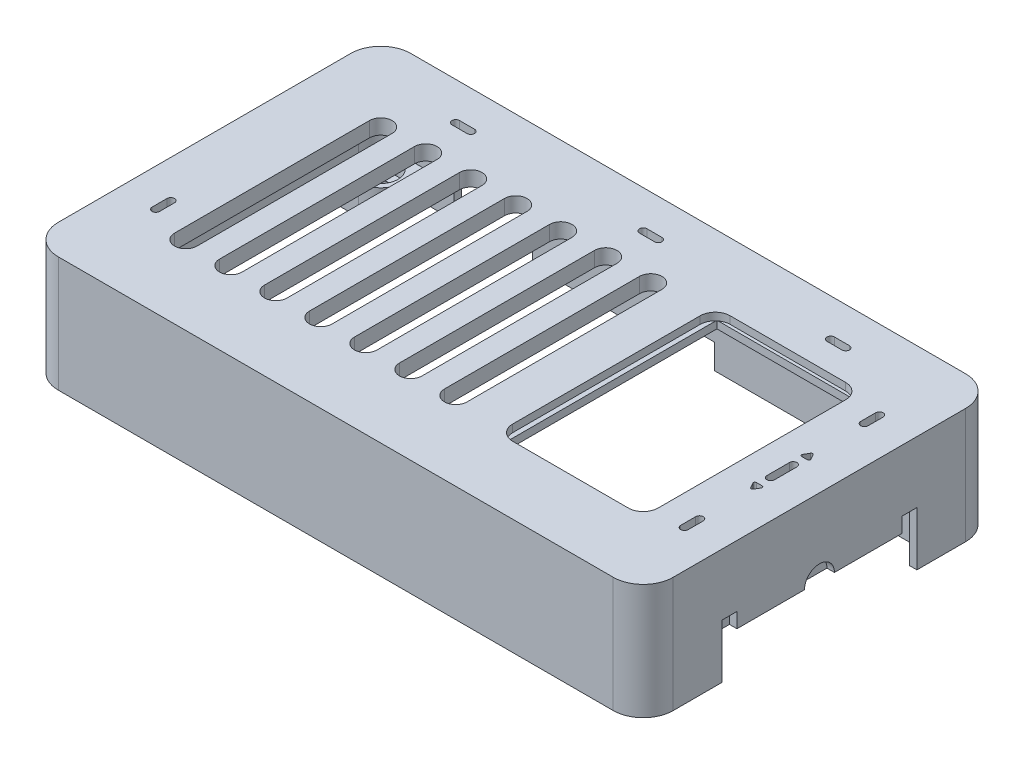
SolidWorks part; units mm, degrees
ref_plane "前视基准面" through (0, 0, 0) normal (0, 0, 1) x (1, 0, 0)
ref_plane "上视基准面" through (0, 0, 0) normal (0, 1, 0) x (1, 0, 0)
ref_plane "右视基准面" through (0, 0, 0) normal (1, 0, 0) x (0, 0, -1)
sketch "草图1" plane through (0, 0, 0) normal (0, 1, 0) x (1, 0, 0)
  line L0 (-1, -3) -> (-1, -42)
  line L1 (3, 0) -> (77, 0) construction
  line L2 (0, -3) -> (0, -42) construction
  line L3 (3, -45) -> (77, -45) construction
  line L4 (80, -3) -> (80, -42) construction
  line L5 (3, -46) -> (77, -46)
  line L6 (81, -3) -> (81, -42)
  line L7 (3, 1) -> (77, 1)
  arc A0 (3, -45) -> (0, -42) centre (3, -42) cw construction
  arc A1 (77, -45) -> (80, -42) centre (77, -42) ccw construction
  arc A2 (80, -3) -> (77, 0) centre (77, -3) ccw construction
  arc A3 (3, 0) -> (0, -3) centre (3, -3) ccw construction
  arc A4 (3, -46) -> (-1, -42) centre (3, -42) cw
  arc A5 (77, -46) -> (81, -42) centre (77, -42) ccw
  arc A6 (81, -3) -> (77, 1) centre (77, -3) ccw
  arc A7 (3, 1) -> (-1, -3) centre (3, -3) ccw
  point P14 (0, 0)
  dimension "D1" = 3
  dimension "D2" = 1
extrude "凸台-拉伸1" add sketch "草图1" against normal blind 2
sketch "草图2" plane through (0, 0, 0) normal (0, 1, 0) x (1, 0, 0)
  line L0 (0, -3) -> (0, -42) construction
  line L1 (3, -45) -> (77, -45) construction
  line L2 (80, -42) -> (80, -3) construction
  line L3 (77, 0) -> (3, 0) construction
  line L4 (-1, -3) -> (-1, -42)
  line L5 (77, 1) -> (3, 1)
  line L6 (81, -42) -> (81, -3)
  line L7 (3, -46) -> (77, -46)
  line L8 (-1, -3) -> (-1, -42) construction
  line L9 (77, 1) -> (3, 1) construction
  line L10 (81, -42) -> (81, -3) construction
  line L11 (3, -46) -> (77, -46) construction
  line L12 (39, -4) -> (41, -4) construction
  line L13 (0, 0) -> (80, 0) construction
  line L14 (0, 0) -> (0, -4) construction
  line L15 (0, -4) -> (80, -4) construction
  line L16 (80, 0) -> (80, -4) construction
  line L17 (39, -3.5) -> (41, -3.5)
  line L18 (39, -4.5) -> (41, -4.5)
  line L19 (0, -4) -> (15, -4) construction
  line L20 (14, -4) -> (16, -4) construction
  line L21 (14, -3.5) -> (16, -3.5)
  line L22 (14, -4.5) -> (16, -4.5)
  line L23 (80, -4) -> (65, -4) construction
  line L24 (64, -4) -> (66, -4) construction
  line L25 (64, -3.5) -> (66, -3.5)
  line L26 (64, -4.5) -> (66, -4.5)
  line L27 (76, -22.5) -> (76, -19.064) construction
  line L28 (80, 0) -> (76, 0) construction
  line L29 (80, 0) -> (80, -45) construction
  line L30 (80, -45) -> (76, -45) construction
  line L31 (76, 0) -> (76, -45) construction
  line L32 (76, -21) -> (76, -24) construction
  line L33 (76.5, -21) -> (76.5, -24)
  line L34 (75.5, -21) -> (75.5, -24)
  line L35 (76, -22.5) -> (76, -25.936) construction
  line L36 (75.8268, -18.514) -> (75.4371, -19.189)
  line L37 (75.6103, -19.489) -> (76.3897, -19.489)
  line L38 (76.5629, -19.189) -> (76.1732, -18.514)
  line L39 (76, -22.5) -> (76, -10.5) construction
  line L40 (76.1732, -26.486) -> (76.5629, -25.811)
  line L41 (76.3897, -25.511) -> (75.6103, -25.511)
  line L42 (75.4371, -25.811) -> (75.8268, -26.486)
  line L43 (76, -9.5) -> (76, -11.5) construction
  line L44 (76.5, -9.5) -> (76.5, -11.5)
  line L45 (75.5, -9.5) -> (75.5, -11.5)
  line L46 (76, -22.5) -> (76, -34.5) construction
  line L47 (76, -33.5) -> (76, -35.5) construction
  line L48 (76.5, -33.5) -> (76.5, -35.5)
  line L49 (75.5, -33.5) -> (75.5, -35.5)
  line L50 (4, 0) -> (4, -33) construction
  line L51 (0, 0) -> (4, 0) construction
  line L52 (0, 0) -> (0, -45) construction
  line L53 (0, -45) -> (4, -45) construction
  line L54 (4, 0) -> (4, -45) construction
  line L55 (4, -32) -> (4, -34) construction
  line L56 (4.5, -32) -> (4.5, -34)
  line L57 (3.5, -32) -> (3.5, -34)
  line L58 (70, -8) -> (54.5978, -8)
  line L59 (80, 0) -> (70, 0) construction
  line L60 (80, 0) -> (80, -10) construction
  line L61 (80, -10) -> (70, -10) construction
  line L62 (70, 0) -> (70, -10) construction
  line L63 (80, -45) -> (70, -45) construction
  line L64 (80, -45) -> (80, -35) construction
  line L65 (80, -35) -> (70, -35) construction
  line L66 (70, -45) -> (70, -35) construction
  line L67 (70, -10) -> (54.5978, -10) construction
  line L68 (70, -10) -> (70, -35) construction
  line L69 (70, -35) -> (54.5978, -35) construction
  line L70 (54.5978, -10) -> (54.5978, -35) construction
  line L71 (52.5978, -10) -> (52.5978, -35)
  line L72 (70, -37) -> (54.5978, -37)
  line L73 (72, -10) -> (72, -35)
  line L74 (72, -37) -> (52.5978, -37) construction
  line L75 (72, -8) -> (72, -37) construction
  line L76 (52.5978, -8) -> (52.5978, -37) construction
  line L77 (72, -8) -> (52.5978, -8) construction
  line L78 (54.5978, -8) -> (70, -8) construction
  line L79 (54.5978, -37) -> (70, -37) construction
  line L80 (8, -8) -> (9.5, -8) construction
  line L85 (0, 0) -> (8, 0) construction
  line L86 (0, 0) -> (0, -8) construction
  line L87 (0, -8) -> (8, -8) construction
  line L88 (8, -0.0281) -> (8, -8.0281) construction
  line L89 (9.5, -9.5) -> (9.5, -35.5) construction
  line L90 (8, -8) -> (9.5, -8) construction
  line L91 (8, -8) -> (8, -9.5) construction
  line L92 (8, -9.5) -> (9.5, -9.5) construction
  line L93 (9.5, -8) -> (9.5, -9.5) construction
  line L94 (8, -37) -> (9.5, -37) construction
  line L95 (8, -37) -> (8, -35.5) construction
  line L96 (8, -35.5) -> (9.5, -35.5) construction
  line L97 (9.5, -37) -> (9.5, -35.5) construction
  line L98 (11, -9.5) -> (11, -35.5)
  line L99 (8, -9.5) -> (8, -35.5)
  line L100 (15.5, -9.5) -> (15.5, -35.5) construction
  line L101 (17, -9.5) -> (17, -35.5)
  line L102 (14, -9.5) -> (14, -35.5)
  line L103 (21.5, -9.5) -> (21.5, -35.5) construction
  line L104 (23, -9.5) -> (23, -35.5)
  line L105 (20, -9.5) -> (20, -35.5)
  line L106 (27.5, -9.5) -> (27.5, -35.5) construction
  line L107 (29, -9.5) -> (29, -35.5)
  line L108 (26, -9.5) -> (26, -35.5)
  line L109 (33.5, -9.5) -> (33.5, -35.5) construction
  line L110 (35, -9.5) -> (35, -35.5)
  line L111 (32, -9.5) -> (32, -35.5)
  line L112 (39.5, -9.5) -> (39.5, -35.5) construction
  line L113 (41, -9.5) -> (41, -35.5)
  line L114 (38, -9.5) -> (38, -35.5)
  line L115 (45.5, -9.5) -> (45.5, -35.5) construction
  line L116 (47, -9.5) -> (47, -35.5)
  line L117 (44, -9.5) -> (44, -35.5)
  arc A0 (0, -42) -> (3, -45) centre (3, -42) ccw construction
  arc A1 (77, -45) -> (80, -42) centre (77, -42) ccw construction
  arc A2 (80, -3) -> (77, 0) centre (77, -3) ccw construction
  arc A3 (3, 0) -> (0, -3) centre (3, -3) ccw construction
  arc A4 (3, 1) -> (-1, -3) centre (3, -3) ccw
  arc A5 (81, -3) -> (77, 1) centre (77, -3) ccw
  arc A6 (77, -46) -> (81, -42) centre (77, -42) ccw
  arc A7 (-1, -42) -> (3, -46) centre (3, -42) ccw
  arc A8 (3, 1) -> (-1, -3) centre (3, -3) ccw construction
  arc A9 (81, -3) -> (77, 1) centre (77, -3) ccw construction
  arc A10 (77, -46) -> (81, -42) centre (77, -42) ccw construction
  arc A11 (-1, -42) -> (3, -46) centre (3, -42) ccw construction
  arc A12 (39, -3.5) -> (39, -4.5) centre (39, -4) ccw
  arc A13 (41, -4.5) -> (41, -3.5) centre (41, -4) ccw
  arc A14 (14, -3.5) -> (14, -4.5) centre (14, -4) ccw
  arc A15 (16, -4.5) -> (16, -3.5) centre (16, -4) ccw
  arc A16 (64, -3.5) -> (64, -4.5) centre (64, -4) ccw
  arc A17 (66, -4.5) -> (66, -3.5) centre (66, -4) ccw
  arc A19 (76.5, -21) -> (75.5, -21) centre (76, -21) ccw
  arc A20 (75.5, -24) -> (76.5, -24) centre (76, -24) ccw
  circle A21 centre (76, -19.064) radius 0.85 construction
  arc A22 (76.5629, -19.189) -> (76.3897, -19.489) centre (76.3897, -19.289) cw
  arc A23 (76.1732, -18.514) -> (75.8268, -18.514) centre (76, -18.614) ccw
  arc A24 (75.4371, -19.189) -> (75.6103, -19.489) centre (75.6103, -19.289) ccw
  circle A25 centre (76, -25.936) radius 0.85 construction
  arc A26 (76.1732, -26.486) -> (75.8268, -26.486) centre (76, -26.386) cw
  arc A27 (76.3897, -25.511) -> (76.5629, -25.811) centre (76.3897, -25.711) cw
  arc A28 (75.6103, -25.511) -> (75.4371, -25.811) centre (75.6103, -25.711) ccw
  arc A29 (76.5, -9.5) -> (75.5, -9.5) centre (76, -9.5) ccw
  arc A30 (75.5, -11.5) -> (76.5, -11.5) centre (76, -11.5) ccw
  arc A31 (76.5, -33.5) -> (75.5, -33.5) centre (76, -33.5) ccw
  arc A32 (75.5, -35.5) -> (76.5, -35.5) centre (76, -35.5) ccw
  arc A33 (4.5, -32) -> (3.5, -32) centre (4, -32) ccw
  arc A34 (3.5, -34) -> (4.5, -34) centre (4, -34) ccw
  arc A35 (70, -37) -> (72, -35) centre (70, -35) ccw
  arc A36 (54.5978, -37) -> (52.5978, -35) centre (54.5978, -35) cw
  arc A37 (72, -10) -> (70, -8) centre (70, -10) ccw
  arc A38 (54.5978, -8) -> (52.5978, -10) centre (54.5978, -10) ccw
  arc A39 (11, -9.5) -> (8, -9.5) centre (9.5, -9.5) ccw
  arc A40 (8, -35.5) -> (11, -35.5) centre (9.5, -35.5) ccw
  arc A41 (17, -9.5) -> (14, -9.5) centre (15.5, -9.5) ccw
  arc A42 (14, -35.5) -> (17, -35.5) centre (15.5, -35.5) ccw
  arc A43 (23, -9.5) -> (20, -9.5) centre (21.5, -9.5) ccw
  arc A44 (20, -35.5) -> (23, -35.5) centre (21.5, -35.5) ccw
  arc A45 (29, -9.5) -> (26, -9.5) centre (27.5, -9.5) ccw
  arc A46 (26, -35.5) -> (29, -35.5) centre (27.5, -35.5) ccw
  arc A47 (35, -9.5) -> (32, -9.5) centre (33.5, -9.5) ccw
  arc A48 (32, -35.5) -> (35, -35.5) centre (33.5, -35.5) ccw
  arc A49 (41, -9.5) -> (38, -9.5) centre (39.5, -9.5) ccw
  arc A50 (38, -35.5) -> (41, -35.5) centre (39.5, -35.5) ccw
  arc A51 (47, -9.5) -> (44, -9.5) centre (45.5, -9.5) ccw
  arc A52 (44, -35.5) -> (47, -35.5) centre (45.5, -35.5) ccw
  point P31 (40, -4)
  point P38 (15, -4)
  point P46 (65, -4)
  point P59 (76, -22.5)
  point P70 (76.7361, -19.489)
  point P86 (75.2639, -25.511)
  point P89 (76, -10.5)
  point P97 (76, -34.5)
  point P109 (4, -33)
  point P154 (9.5, -22.5)
  point P162 (15.5, -22.5)
  point P169 (21.5, -22.5)
  point P176 (27.5, -22.5)
  point P183 (33.5, -22.5)
  point P190 (39.5, -22.5)
  point P197 (45.5, -22.5)
  dimension "D3" = 0.2
  dimension "D4" = 0.2
  dimension "D5" = 2
  dimension "D6" = 2
  dimension "D7" = 7
  dimension "D1" = 0
  dimension "D2" = 1
extrude "切除-拉伸1" cut sketch "草图2" against normal blind 1
sketch "草图3" plane through (0, -2, 0) normal (0, -1, 0) x (1, 0, 0)
  line L0 (76, 11.5) -> (76, 9.5) construction
  line L1 (76, 24) -> (76, 21) construction
  line L2 (14, 3.5) -> (16, 3.5)
  line L3 (16, 4.5) -> (14, 4.5)
  line L4 (14, 3.5) -> (16, 3.5) construction
  line L5 (16, 4.5) -> (14, 4.5) construction
  line L6 (39, 3.5) -> (41, 3.5)
  line L7 (41, 4.5) -> (39, 4.5)
  line L8 (39, 3.5) -> (41, 3.5) construction
  line L9 (41, 4.5) -> (39, 4.5) construction
  line L10 (76.5, 21) -> (76.5, 24)
  line L11 (75.5, 24) -> (75.5, 21)
  line L12 (76.5, 21) -> (76.5, 24) construction
  line L13 (75.5, 24) -> (75.5, 21) construction
  line L14 (64, 3.5) -> (66, 3.5)
  line L15 (66, 4.5) -> (64, 4.5)
  line L16 (64, 3.5) -> (66, 3.5) construction
  line L17 (66, 4.5) -> (64, 4.5) construction
  line L18 (76.5, 9.5) -> (76.5, 11.5)
  line L19 (75.4371, 19.189) -> (75.8268, 18.514)
  line L20 (76.3897, 19.489) -> (75.6103, 19.489)
  line L21 (76.1732, 18.514) -> (76.5629, 19.189)
  line L22 (75.4371, 19.189) -> (75.8268, 18.514) construction
  line L23 (76.3897, 19.489) -> (75.6103, 19.489) construction
  line L24 (76.1732, 18.514) -> (76.5629, 19.189) construction
  line L25 (75.5, 11.5) -> (75.5, 9.5)
  line L26 (76.5, 9.5) -> (76.5, 11.5) construction
  line L27 (75.5, 11.5) -> (75.5, 9.5) construction
  line L28 (76.5, 33.5) -> (76.5, 35.5)
  line L29 (76.5629, 25.811) -> (76.1732, 26.486)
  line L30 (75.8268, 26.486) -> (75.4371, 25.811)
  line L31 (75.6103, 25.511) -> (76.3897, 25.511)
  line L32 (76.5629, 25.811) -> (76.1732, 26.486) construction
  line L33 (75.8268, 26.486) -> (75.4371, 25.811) construction
  line L34 (75.6103, 25.511) -> (76.3897, 25.511) construction
  line L35 (75.5, 35.5) -> (75.5, 33.5)
  line L36 (76.5, 33.5) -> (76.5, 35.5) construction
  line L37 (75.5, 35.5) -> (75.5, 33.5) construction
  line L38 (3.5, 34) -> (3.5, 32)
  line L39 (4.5, 32) -> (4.5, 34)
  line L40 (3.5, 34) -> (3.5, 32) construction
  line L41 (4.5, 32) -> (4.5, 34) construction
  line L42 (11, 9.5) -> (11, 35.5)
  line L43 (8, 35.5) -> (8, 9.5)
  line L44 (54.5978, 8) -> (70, 8)
  line L45 (52.5978, 35) -> (52.5978, 10)
  line L46 (70, 37) -> (54.5978, 37)
  line L47 (72, 10) -> (72, 35)
  line L48 (54.5978, 8) -> (70, 8) construction
  line L49 (52.5978, 35) -> (52.5978, 10) construction
  line L50 (70, 37) -> (54.5978, 37) construction
  line L51 (72, 10) -> (72, 35) construction
  line L52 (11, 9.5) -> (11, 35.5) construction
  line L53 (8, 35.5) -> (8, 9.5) construction
  line L54 (23, 9.5) -> (23, 35.5)
  line L55 (20, 35.5) -> (20, 9.5)
  line L56 (23, 9.5) -> (23, 35.5) construction
  line L57 (20, 35.5) -> (20, 9.5) construction
  line L58 (17, 9.5) -> (17, 35.5)
  line L59 (14, 35.5) -> (14, 9.5)
  line L60 (17, 9.5) -> (17, 35.5) construction
  line L61 (14, 35.5) -> (14, 9.5) construction
  line L62 (35, 9.5) -> (35, 35.5)
  line L63 (32, 35.5) -> (32, 9.5)
  line L64 (35, 9.5) -> (35, 35.5) construction
  line L65 (32, 35.5) -> (32, 9.5) construction
  line L66 (29, 9.5) -> (29, 35.5)
  line L67 (26, 35.5) -> (26, 9.5)
  line L68 (29, 9.5) -> (29, 35.5) construction
  line L69 (26, 35.5) -> (26, 9.5) construction
  line L70 (47, 9.5) -> (47, 35.5)
  line L71 (44, 35.5) -> (44, 9.5)
  line L72 (47, 9.5) -> (47, 35.5) construction
  line L73 (44, 35.5) -> (44, 9.5) construction
  line L74 (38, 35.5) -> (38, 9.5)
  line L75 (41, 9.5) -> (41, 35.5)
  line L76 (38, 35.5) -> (38, 9.5) construction
  line L77 (41, 9.5) -> (41, 35.5) construction
  line L78 (74.75, 20.314) -> (77.25, 20.314)
  line L79 (74.75, 21.25) -> (77.25, 21.25)
  line L80 (74.75, 21.25) -> (74.75, 23.75)
  line L81 (74.75, 23.75) -> (77.25, 23.75)
  line L82 (77.25, 21.25) -> (77.25, 23.75)
  line L83 (74.75, 21.25) -> (77.25, 23.75) construction
  line L84 (74.75, 23.75) -> (77.25, 21.25) construction
  line L85 (74.75, 24.686) -> (77.25, 24.686)
  line L86 (74.75, 24.686) -> (74.75, 27.186)
  line L87 (74.75, 27.186) -> (77.25, 27.186)
  line L88 (77.25, 24.686) -> (77.25, 27.186)
  line L89 (74.75, 24.686) -> (77.25, 27.186) construction
  line L90 (74.75, 27.186) -> (77.25, 24.686) construction
  line L91 (74.75, 20.314) -> (74.75, 17.814)
  line L92 (74.75, 17.814) -> (77.25, 17.814)
  line L93 (77.25, 20.314) -> (77.25, 17.814)
  line L94 (74.75, 20.314) -> (77.25, 17.814) construction
  line L95 (74.75, 17.814) -> (77.25, 20.314) construction
  line L96 (76, 35.5) -> (76, 33.5) construction
  line L97 (74.75, 11.75) -> (77.25, 11.75)
  line L98 (74.75, 11.75) -> (74.75, 9.25)
  line L99 (74.75, 9.25) -> (77.25, 9.25)
  line L100 (77.25, 11.75) -> (77.25, 9.25)
  line L101 (74.75, 11.75) -> (77.25, 9.25) construction
  line L102 (74.75, 9.25) -> (77.25, 11.75) construction
  line L103 (64, 4) -> (66, 4) construction
  line L104 (74.75, 35.75) -> (77.25, 35.75)
  line L105 (74.75, 35.75) -> (74.75, 33.25)
  line L106 (74.75, 33.25) -> (77.25, 33.25)
  line L107 (77.25, 35.75) -> (77.25, 33.25)
  line L108 (74.75, 35.75) -> (77.25, 33.25) construction
  line L109 (74.75, 33.25) -> (77.25, 35.75) construction
  line L110 (39, 4) -> (41, 4) construction
  line L111 (14, 4) -> (16, 4) construction
  line L112 (4, 34) -> (4, 32) construction
  line L115 (63.75, 5.25) -> (63.75, 2.75)
  line L116 (63.75, 2.75) -> (66.25, 2.75)
  line L117 (66.25, 5.25) -> (66.25, 2.75)
  line L118 (63.75, 5.25) -> (66.25, 2.75) construction
  line L119 (63.75, 2.75) -> (66.25, 5.25) construction
  line L121 (38.75, 5.25) -> (38.75, 2.75)
  line L122 (38.75, 2.75) -> (41.25, 2.75)
  line L123 (41.25, 5.25) -> (41.25, 2.75)
  line L124 (38.75, 5.25) -> (41.25, 2.75) construction
  line L125 (38.75, 2.75) -> (41.25, 5.25) construction
  line L127 (13.75, 5.25) -> (13.75, 2.75)
  line L128 (13.75, 2.75) -> (16.25, 2.75)
  line L129 (16.25, 5.25) -> (16.25, 2.75)
  line L130 (13.75, 5.25) -> (16.25, 2.75) construction
  line L131 (13.75, 2.75) -> (16.25, 5.25) construction
  line L132 (2.75, 34.25) -> (5.25, 34.25)
  line L133 (2.75, 34.25) -> (2.75, 31.75)
  line L134 (2.75, 31.75) -> (5.25, 31.75)
  line L135 (5.25, 34.25) -> (5.25, 31.75)
  line L136 (2.75, 34.25) -> (5.25, 31.75) construction
  line L137 (2.75, 31.75) -> (5.25, 34.25) construction
  line L138 (70, 10) -> (71.37, 10) construction
  line L139 (70, 10) -> (70, 8.4) construction
  line L140 (70, 8.4) -> (71.37, 8.4) construction
  line L141 (71.37, 10) -> (71.37, 8.4) construction
  line L142 (54.5978, 10) -> (53.2278, 10) construction
  line L143 (54.5978, 10) -> (54.5978, 8.4) construction
  line L144 (54.5978, 8.4) -> (53.2278, 8.4) construction
  line L145 (3, 0) -> (77, 0)
  line L146 (80, 3) -> (80, 42)
  line L147 (77, 45) -> (3, 45)
  line L148 (0, 42) -> (0, 3)
  line L149 (3, 0) -> (77, 0) construction
  line L150 (80, 3) -> (80, 42) construction
  line L151 (77, 45) -> (3, 45) construction
  line L152 (0, 42) -> (0, 3) construction
  line L153 (53.2278, 10) -> (53.2278, 8.4) construction
  line L154 (53.2278, 8.4) -> (71.37, 8.4)
  line L155 (53.2278, 8.4) -> (53.2278, 40.4)
  line L156 (53.2278, 40.4) -> (71.37, 40.4)
  line L157 (71.37, 8.4) -> (71.37, 40.4)
  line L159 (13.75, 5.25) -> (13.75, 6.25)
  line L160 (13.75, 6.25) -> (16.25, 6.25)
  line L161 (16.25, 5.25) -> (16.25, 6.25)
  line L163 (38.75, 5.25) -> (38.75, 6.25)
  line L164 (38.75, 6.25) -> (41.25, 6.25)
  line L165 (41.25, 5.25) -> (41.25, 6.25)
  line L167 (63.75, 5.25) -> (63.75, 6.25)
  line L168 (63.75, 6.25) -> (66.25, 6.25)
  line L169 (66.25, 5.25) -> (66.25, 6.25)
  circle A0 centre (76, 25.936) radius 0.45 construction
  circle A1 centre (76, 19.064) radius 0.45 construction
  arc A2 (16, 3.5) -> (16, 4.5) centre (16, 4) ccw
  arc A3 (14, 4.5) -> (14, 3.5) centre (14, 4) ccw
  arc A4 (16, 3.5) -> (16, 4.5) centre (16, 4) ccw construction
  arc A5 (14, 4.5) -> (14, 3.5) centre (14, 4) ccw construction
  arc A6 (41, 3.5) -> (41, 4.5) centre (41, 4) ccw
  arc A7 (39, 4.5) -> (39, 3.5) centre (39, 4) ccw
  arc A8 (41, 3.5) -> (41, 4.5) centre (41, 4) ccw construction
  arc A9 (39, 4.5) -> (39, 3.5) centre (39, 4) ccw construction
  arc A10 (76.5, 24) -> (75.5, 24) centre (76, 24) ccw
  arc A11 (75.5, 21) -> (76.5, 21) centre (76, 21) ccw
  arc A12 (76.5, 24) -> (75.5, 24) centre (76, 24) ccw construction
  arc A13 (75.5, 21) -> (76.5, 21) centre (76, 21) ccw construction
  arc A14 (66, 3.5) -> (66, 4.5) centre (66, 4) ccw
  arc A15 (64, 4.5) -> (64, 3.5) centre (64, 4) ccw
  arc A16 (66, 3.5) -> (66, 4.5) centre (66, 4) ccw construction
  arc A17 (64, 4.5) -> (64, 3.5) centre (64, 4) ccw construction
  arc A18 (76.5, 11.5) -> (75.5, 11.5) centre (76, 11.5) ccw
  arc A19 (75.6103, 19.489) -> (75.4371, 19.189) centre (75.6103, 19.289) ccw
  arc A20 (76.5629, 19.189) -> (76.3897, 19.489) centre (76.3897, 19.289) ccw
  arc A21 (75.8268, 18.514) -> (76.1732, 18.514) centre (76, 18.614) ccw
  arc A22 (75.6103, 19.489) -> (75.4371, 19.189) centre (75.6103, 19.289) ccw construction
  arc A23 (76.5629, 19.189) -> (76.3897, 19.489) centre (76.3897, 19.289) ccw construction
  arc A24 (75.8268, 18.514) -> (76.1732, 18.514) centre (76, 18.614) ccw construction
  arc A25 (75.5, 9.5) -> (76.5, 9.5) centre (76, 9.5) ccw
  arc A26 (76.5, 11.5) -> (75.5, 11.5) centre (76, 11.5) ccw construction
  arc A27 (75.5, 9.5) -> (76.5, 9.5) centre (76, 9.5) ccw construction
  arc A28 (76.5, 35.5) -> (75.5, 35.5) centre (76, 35.5) ccw
  arc A29 (76.1732, 26.486) -> (75.8268, 26.486) centre (76, 26.386) ccw
  arc A30 (75.4371, 25.811) -> (75.6103, 25.511) centre (75.6103, 25.711) ccw
  arc A31 (76.3897, 25.511) -> (76.5629, 25.811) centre (76.3897, 25.711) ccw
  arc A32 (76.1732, 26.486) -> (75.8268, 26.486) centre (76, 26.386) ccw construction
  arc A33 (75.4371, 25.811) -> (75.6103, 25.511) centre (75.6103, 25.711) ccw construction
  arc A34 (76.3897, 25.511) -> (76.5629, 25.811) centre (76.3897, 25.711) ccw construction
  arc A35 (75.5, 33.5) -> (76.5, 33.5) centre (76, 33.5) ccw
  arc A36 (76.5, 35.5) -> (75.5, 35.5) centre (76, 35.5) ccw construction
  arc A37 (75.5, 33.5) -> (76.5, 33.5) centre (76, 33.5) ccw construction
  arc A38 (4.5, 34) -> (3.5, 34) centre (4, 34) ccw
  arc A39 (3.5, 32) -> (4.5, 32) centre (4, 32) ccw
  arc A40 (4.5, 34) -> (3.5, 34) centre (4, 34) ccw construction
  arc A41 (3.5, 32) -> (4.5, 32) centre (4, 32) ccw construction
  arc A42 (11, 35.5) -> (8, 35.5) centre (9.5, 35.5) ccw
  arc A43 (8, 9.5) -> (11, 9.5) centre (9.5, 9.5) ccw
  arc A44 (52.5978, 10) -> (54.5978, 8) centre (54.5978, 10) ccw
  arc A45 (54.5978, 37) -> (52.5978, 35) centre (54.5978, 35) ccw
  arc A46 (72, 35) -> (70, 37) centre (70, 35) ccw
  arc A47 (70, 8) -> (72, 10) centre (70, 10) ccw
  arc A48 (52.5978, 10) -> (54.5978, 8) centre (54.5978, 10) ccw construction
  arc A49 (54.5978, 37) -> (52.5978, 35) centre (54.5978, 35) ccw construction
  arc A50 (72, 35) -> (70, 37) centre (70, 35) ccw construction
  arc A51 (70, 8) -> (72, 10) centre (70, 10) ccw construction
  arc A52 (11, 35.5) -> (8, 35.5) centre (9.5, 35.5) ccw construction
  arc A53 (8, 9.5) -> (11, 9.5) centre (9.5, 9.5) ccw construction
  arc A54 (23, 35.5) -> (20, 35.5) centre (21.5, 35.5) ccw
  arc A55 (20, 9.5) -> (23, 9.5) centre (21.5, 9.5) ccw
  arc A56 (23, 35.5) -> (20, 35.5) centre (21.5, 35.5) ccw construction
  arc A57 (20, 9.5) -> (23, 9.5) centre (21.5, 9.5) ccw construction
  arc A58 (17, 35.5) -> (14, 35.5) centre (15.5, 35.5) ccw
  arc A59 (14, 9.5) -> (17, 9.5) centre (15.5, 9.5) ccw
  arc A60 (17, 35.5) -> (14, 35.5) centre (15.5, 35.5) ccw construction
  arc A61 (14, 9.5) -> (17, 9.5) centre (15.5, 9.5) ccw construction
  arc A62 (35, 35.5) -> (32, 35.5) centre (33.5, 35.5) ccw
  arc A63 (32, 9.5) -> (35, 9.5) centre (33.5, 9.5) ccw
  arc A64 (35, 35.5) -> (32, 35.5) centre (33.5, 35.5) ccw construction
  arc A65 (32, 9.5) -> (35, 9.5) centre (33.5, 9.5) ccw construction
  arc A66 (29, 35.5) -> (26, 35.5) centre (27.5, 35.5) ccw
  arc A67 (26, 9.5) -> (29, 9.5) centre (27.5, 9.5) ccw
  arc A68 (29, 35.5) -> (26, 35.5) centre (27.5, 35.5) ccw construction
  arc A69 (26, 9.5) -> (29, 9.5) centre (27.5, 9.5) ccw construction
  arc A70 (47, 35.5) -> (44, 35.5) centre (45.5, 35.5) ccw
  arc A71 (44, 9.5) -> (47, 9.5) centre (45.5, 9.5) ccw
  arc A72 (47, 35.5) -> (44, 35.5) centre (45.5, 35.5) ccw construction
  arc A73 (44, 9.5) -> (47, 9.5) centre (45.5, 9.5) ccw construction
  arc A74 (41, 35.5) -> (38, 35.5) centre (39.5, 35.5) ccw
  arc A75 (38, 9.5) -> (41, 9.5) centre (39.5, 9.5) ccw
  arc A76 (41, 35.5) -> (38, 35.5) centre (39.5, 35.5) ccw construction
  arc A77 (38, 9.5) -> (41, 9.5) centre (39.5, 9.5) ccw construction
  arc A86 (0, 3) -> (3, 0) centre (3, 3) ccw
  arc A87 (77, 0) -> (80, 3) centre (77, 3) ccw
  arc A88 (80, 42) -> (77, 45) centre (77, 42) ccw
  arc A89 (3, 45) -> (0, 42) centre (3, 42) ccw
  arc A90 (0, 3) -> (3, 0) centre (3, 3) ccw construction
  arc A91 (77, 0) -> (80, 3) centre (77, 3) ccw construction
  arc A92 (80, 42) -> (77, 45) centre (77, 42) ccw construction
  arc A93 (3, 45) -> (0, 42) centre (3, 42) ccw construction
  point P104 (76, 22.5)
  point P131 (76, 10.5)
  point P136 (76, 34.5)
  point P141 (65, 4)
  point P146 (40, 4)
  point P151 (15, 4)
  point P156 (4, 33)
  dimension "D18" = 1
  dimension "D1" = 0
  dimension "D2" = 0
  dimension "D3" = 0
  dimension "D4" = 0
  dimension "D5" = 0
  dimension "D6" = 0
  dimension "D7" = 0
  dimension "D8" = 0
  dimension "D9" = 0
  dimension "D10" = 0
  dimension "D11" = 0
  dimension "D12" = 0
  dimension "D13" = 0
  dimension "D14" = 0
  dimension "D15" = 0
  dimension "D16" = 0
  dimension "D17" = 0
extrude "切除-拉伸2" cut sketch "草图3" against normal blind 1
sketch "草图4" plane through (0, 0, 0) normal (0, 1, 0) x (1, 0, 0)
  line L42 (11, -35.5) -> (11, -9.5)
  line L43 (8, -9.5) -> (8, -35.5)
  line L52 (11, -35.5) -> (11, -9.5)
  line L53 (8, -9.5) -> (8, -35.5)
  line L54 (23, -35.5) -> (23, -9.5)
  line L55 (20, -9.5) -> (20, -35.5)
  line L56 (23, -35.5) -> (23, -9.5)
  line L57 (20, -9.5) -> (20, -35.5)
  line L58 (17, -35.5) -> (17, -9.5)
  line L59 (14, -9.5) -> (14, -35.5)
  line L60 (17, -35.5) -> (17, -9.5)
  line L61 (14, -9.5) -> (14, -35.5)
  line L62 (35, -35.5) -> (35, -9.5)
  line L63 (32, -9.5) -> (32, -35.5)
  line L64 (35, -35.5) -> (35, -9.5)
  line L65 (32, -9.5) -> (32, -35.5)
  line L66 (29, -35.5) -> (29, -9.5)
  line L67 (26, -9.5) -> (26, -35.5)
  line L68 (29, -35.5) -> (29, -9.5)
  line L69 (26, -9.5) -> (26, -35.5)
  line L70 (47, -35.5) -> (47, -9.5)
  line L71 (44, -9.5) -> (44, -35.5)
  line L72 (47, -35.5) -> (47, -9.5)
  line L73 (44, -9.5) -> (44, -35.5)
  line L74 (38, -9.5) -> (38, -35.5)
  line L75 (41, -35.5) -> (41, -9.5)
  line L76 (38, -9.5) -> (38, -35.5)
  line L77 (41, -35.5) -> (41, -9.5)
  arc A42 (8, -35.5) -> (11, -35.5) centre (9.5, -35.5) ccw
  arc A43 (11, -9.5) -> (8, -9.5) centre (9.5, -9.5) ccw
  arc A52 (8, -35.5) -> (11, -35.5) centre (9.5, -35.5) ccw
  arc A53 (11, -9.5) -> (8, -9.5) centre (9.5, -9.5) ccw
  arc A54 (20, -35.5) -> (23, -35.5) centre (21.5, -35.5) ccw
  arc A55 (23, -9.5) -> (20, -9.5) centre (21.5, -9.5) ccw
  arc A56 (20, -35.5) -> (23, -35.5) centre (21.5, -35.5) ccw
  arc A57 (23, -9.5) -> (20, -9.5) centre (21.5, -9.5) ccw
  arc A58 (14, -35.5) -> (17, -35.5) centre (15.5, -35.5) ccw
  arc A59 (17, -9.5) -> (14, -9.5) centre (15.5, -9.5) ccw
  arc A60 (14, -35.5) -> (17, -35.5) centre (15.5, -35.5) ccw
  arc A61 (17, -9.5) -> (14, -9.5) centre (15.5, -9.5) ccw
  arc A62 (32, -35.5) -> (35, -35.5) centre (33.5, -35.5) ccw
  arc A63 (35, -9.5) -> (32, -9.5) centre (33.5, -9.5) ccw
  arc A64 (32, -35.5) -> (35, -35.5) centre (33.5, -35.5) ccw
  arc A65 (35, -9.5) -> (32, -9.5) centre (33.5, -9.5) ccw
  arc A66 (26, -35.5) -> (29, -35.5) centre (27.5, -35.5) ccw
  arc A67 (29, -9.5) -> (26, -9.5) centre (27.5, -9.5) ccw
  arc A68 (26, -35.5) -> (29, -35.5) centre (27.5, -35.5) ccw
  arc A69 (29, -9.5) -> (26, -9.5) centre (27.5, -9.5) ccw
  arc A70 (44, -35.5) -> (47, -35.5) centre (45.5, -35.5) ccw
  arc A71 (47, -9.5) -> (44, -9.5) centre (45.5, -9.5) ccw
  arc A72 (44, -35.5) -> (47, -35.5) centre (45.5, -35.5) ccw
  arc A73 (47, -9.5) -> (44, -9.5) centre (45.5, -9.5) ccw
  arc A74 (38, -35.5) -> (41, -35.5) centre (39.5, -35.5) ccw
  arc A75 (41, -9.5) -> (38, -9.5) centre (39.5, -9.5) ccw
  arc A76 (38, -35.5) -> (41, -35.5) centre (39.5, -35.5) ccw
  arc A77 (41, -9.5) -> (38, -9.5) centre (39.5, -9.5) ccw
  dimension "D11" = 0
  dimension "D12" = 0
  dimension "D13" = 0
  dimension "D14" = 0
  dimension "D15" = 0
  dimension "D16" = 0
  dimension "D17" = 0
extrude "切除-拉伸3" cut sketch "草图4" against normal through all
sketch "草图5" plane through (0, -2, 0) normal (0, -1, 0) x (1, 0, 0)
  line L4 (3, -1) -> (77, -1)
  line L5 (81, 3) -> (81, 42)
  line L6 (77, 46) -> (3, 46)
  line L7 (-1, 42) -> (-1, 3)
  line L8 (3, 0) -> (77, 0)
  line L9 (80, 3) -> (80, 42)
  line L10 (77, 45) -> (3, 45)
  line L11 (0, 42) -> (0, 3)
  line L12 (3, 0) -> (77, 0)
  line L13 (80, 3) -> (80, 42)
  line L14 (77, 45) -> (3, 45)
  line L15 (0, 42) -> (0, 3)
  arc A4 (-1, 3) -> (3, -1) centre (3, 3) ccw
  arc A5 (77, -1) -> (81, 3) centre (77, 3) ccw
  arc A6 (81, 42) -> (77, 46) centre (77, 42) ccw
  arc A7 (3, 46) -> (-1, 42) centre (3, 42) ccw
  arc A8 (0, 3) -> (3, 0) centre (3, 3) ccw
  arc A9 (77, 0) -> (80, 3) centre (77, 3) ccw
  arc A10 (80, 42) -> (77, 45) centre (77, 42) ccw
  arc A11 (3, 45) -> (0, 42) centre (3, 42) ccw
  arc A12 (0, 3) -> (3, 0) centre (3, 3) ccw
  arc A13 (77, 0) -> (80, 3) centre (77, 3) ccw
  arc A14 (80, 42) -> (77, 45) centre (77, 42) ccw
  arc A15 (3, 45) -> (0, 42) centre (3, 42) ccw
  dimension "D1" = 1
  dimension "D2" = 1
extrude "凸台-拉伸2" add sketch "草图5" along normal blind 13.4
sketch "草图6" plane through (0, -15.4, 0) normal (0, -1, 0) x (1, 0, 0)
  line L0 (0, 0) -> (0, 33) construction
  line L1 (0, 42) -> (0, 3) construction
  line L2 (0, 33) -> (-0.5, 33) construction
  line L3 (0, 0) -> (15, 0) construction
  line L4 (-1, 38.25) -> (0, 38.25)
  line L5 (-1, 38.25) -> (-1, 27.75)
  line L6 (-1, 27.75) -> (0, 27.75)
  line L7 (0, 38.25) -> (0, 27.75)
  line L8 (-1, 38.25) -> (0, 27.75) construction
  line L9 (-1, 27.75) -> (0, 38.25) construction
  line L10 (3, 0) -> (77, 0) construction
  line L11 (15, 0) -> (15, -0.5) construction
  line L12 (3, -1) -> (77, -1) construction
  line L13 (9.75, 0) -> (20.25, 0)
  line L14 (9.75, 0) -> (9.75, -1)
  line L15 (9.75, -1) -> (20.25, -1)
  line L16 (20.25, 0) -> (20.25, -1)
  line L17 (9.75, 0) -> (20.25, -1) construction
  line L18 (9.75, -1) -> (20.25, 0) construction
extrude "切除-拉伸4" cut sketch "草图6" against normal blind 10.5
sketch "草图7" plane through (0, -15.4, 0) normal (0, -1, 0) x (1, 0, 0)
  line L0 (40, 0) -> (40, -0.5) construction
  line L1 (3, 0) -> (77, 0) construction
  line L2 (20.25, -1) -> (77, -1) construction
  line L3 (35.5, 0) -> (44.5, 0)
  line L4 (35.5, 0) -> (35.5, -1)
  line L5 (35.5, -1) -> (44.5, -1)
  line L6 (44.5, 0) -> (44.5, -1)
  line L7 (35.5, 0) -> (44.5, -1) construction
  line L8 (35.5, -1) -> (44.5, 0) construction
  line L10 (80, 3) -> (80, 42) construction
  line L11 (44.5, 0) -> (77, 0) construction
  line L12 (80, 0) -> (65, 0) construction
  line L13 (65, 0) -> (65, -0.5) construction
  line L15 (60.5, 0) -> (69.5, 0)
  line L16 (60.5, 0) -> (60.5, -1)
  line L17 (60.5, -1) -> (69.5, -1)
  line L18 (69.5, 0) -> (69.5, -1)
  line L19 (60.5, 0) -> (69.5, -1) construction
  line L20 (60.5, -1) -> (69.5, 0) construction
extrude "切除-拉伸5" cut sketch "草图7" against normal blind 3.3
sketch "草图8" plane through (0, -15.4, 0) normal (0, -1, 0) x (1, 0, 0)
  line L0 (81, 22.5) -> (80.5, 22.5) construction
  line L5 (81, 3) -> (81, 42) construction
  line L7 (80, 9.5) -> (81, 9.5)
  line L8 (80, 9.5) -> (80, 35.5)
  line L9 (80, 35.5) -> (81, 35.5)
  line L10 (81, 9.5) -> (81, 35.5)
  line L11 (80, 9.5) -> (81, 35.5) construction
  line L12 (80, 35.5) -> (81, 9.5) construction
extrude "切除-拉伸6" cut sketch "草图8" against normal blind 5.2
sketch "草图9" plane through (81, 0, 0) normal (1, 0, 0) x (0, 0, -1)
  line L0 (-9.5, -10.2) -> (-35.5, -10.2) construction
  line L1 (-22.5, -10.2) -> (-10.5, -10.2) construction
  line L2 (-22.5, -10.2) -> (-34.5, -10.2) construction
  line L3 (-35.5, -10.2) -> (-35.5, -15.4) construction
  line L4 (-33.5, -8.2) -> (-35.5, -8.2)
  line L5 (-33.5, -8.2) -> (-33.5, -12.2)
  line L6 (-33.5, -12.2) -> (-35.5, -12.2)
  line L7 (-35.5, -8.2) -> (-35.5, -12.2)
  line L8 (-33.5, -8.2) -> (-35.5, -12.2) construction
  line L9 (-33.5, -12.2) -> (-35.5, -8.2) construction
  line L10 (-9.5, -10.2) -> (-9.5, -15.4) construction
  line L11 (-11.5, -8.2) -> (-9.5, -8.2)
  line L12 (-11.5, -8.2) -> (-11.5, -12.2)
  line L13 (-11.5, -12.2) -> (-9.5, -12.2)
  line L14 (-9.5, -8.2) -> (-9.5, -12.2)
  line L15 (-11.5, -8.2) -> (-9.5, -12.2) construction
  line L16 (-11.5, -12.2) -> (-9.5, -8.2) construction
  circle A0 centre (-22.5, -10.2) radius 2
extrude "切除-拉伸7" cut sketch "草图9" against normal up to next
sketch "草图17" plane through (80, 0, 0) normal (-1, 0, 0) x (0, 0, 1)
  line L0 (7, -5.2) -> (7, -14.2)
  line L1 (7, -5.2) -> (38, -5.2) construction
  line L2 (7, -5.2) -> (7, -15.2) construction
  line L3 (7, -15.2) -> (38, -15.2) construction
  line L4 (38, -5.2) -> (38, -15.2) construction
  line L5 (7, -5.2) -> (38, -15.2) construction
  line L6 (7, -15.2) -> (38, -5.2) construction
  line L7 (7, -5.2) -> (37, -5.2) construction
  line L8 (7, -5.2) -> (7, -6.2) construction
  line L9 (8, -6.2) -> (37, -6.2) construction
  line L10 (37, -5.2) -> (37, -6.2) construction
  line L11 (7, -5.2) -> (8, -5.2) construction
  line L12 (7, -5.2) -> (7, -14.2) construction
  line L13 (7, -14.2) -> (8, -14.2) construction
  line L14 (8, -6.2) -> (8, -14.2) construction
  line L15 (7, -14.2) -> (8, -14.2)
  line L16 (8, -14.2) -> (8, -6.2)
  line L17 (8, -6.2) -> (37, -6.2)
  line L18 (37, -6.2) -> (37, -5.2)
  line L19 (37, -5.2) -> (7, -5.2)
  point P0 (22.5, -10.2)
extrude "凸台-拉伸4" add sketch "草图17" along normal blind 4
sketch "草图18" plane through (76, 0, 0) normal (-1, 0, 0) x (0, 0, 1)
  line L0 (7, -14.2) -> (8, -14.2) construction
  line L1 (37, -5.2) -> (37, -6.2) construction
  line L3 (7, -5.2) -> (37, -5.2)
  line L4 (7, -5.2) -> (7, -14.2)
  line L5 (7, -14.2) -> (37, -14.2)
  line L6 (37, -5.2) -> (37, -14.2)
extrude "凸台-拉伸5" add sketch "草图18" along normal blind 1.5
sketch "草图19" plane through (0, -15.4, 0) normal (0, -1, 0) x (1, 0, 0)
  line L0 (3, 39) -> (0, 39)
  line L1 (0, 42) -> (0, 3) construction
  line L2 (0, 39) -> (0, 42)
  line L3 (6, 42) -> (6, 45)
  line L4 (-1, 42) -> (-1, 3)
  line L5 (3, -1) -> (77, -1)
  line L6 (81, 3) -> (81, 42)
  line L7 (77, 46) -> (3, 46)
  line L8 (-1, 42) -> (-1, 3) construction
  line L9 (3, -1) -> (77, -1) construction
  line L10 (81, 3) -> (81, 42) construction
  line L11 (77, 46) -> (3, 46) construction
  line L12 (77, 45) -> (3, 45) construction
  line L13 (6, 45) -> (3, 45)
  line L14 (3, 6) -> (0, 6)
  line L15 (0, 6) -> (0, 3)
  line L16 (6, 3) -> (6, 0)
  line L17 (3, 0) -> (9.75, 0) construction
  line L18 (6, 0) -> (3, 0)
  line L19 (77, 6) -> (80, 6)
  line L20 (80, 3) -> (80, 9.5) construction
  line L21 (80, 6) -> (80, 3)
  line L22 (74, 3) -> (74, 0)
  line L23 (69.5, 0) -> (77, 0) construction
  line L24 (74, 0) -> (77, 0)
  line L25 (74, 42) -> (74, 45)
  line L26 (74, 45) -> (77, 45)
  line L27 (77, 39) -> (80, 39)
  line L28 (80, 3) -> (80, 42) construction
  line L29 (80, 39) -> (80, 42)
  arc A0 (3, 45) -> (0, 42) centre (3, 42) ccw
  arc A1 (74, 42) -> (77, 39) centre (77, 42) ccw
  arc A2 (0, 3) -> (3, 0) centre (3, 3) ccw
  arc A3 (77, 6) -> (74, 3) centre (77, 3) ccw
  arc A4 (-1, 3) -> (3, -1) centre (3, 3) ccw
  arc A5 (77, -1) -> (81, 3) centre (77, 3) ccw
  arc A6 (81, 42) -> (77, 46) centre (77, 42) ccw
  arc A7 (3, 46) -> (-1, 42) centre (3, 42) ccw
  arc A8 (-1, 3) -> (3, -1) centre (3, 3) ccw construction
  arc A9 (77, -1) -> (81, 3) centre (77, 3) ccw construction
  arc A10 (81, 42) -> (77, 46) centre (77, 42) ccw construction
  arc A11 (3, 46) -> (-1, 42) centre (3, 42) ccw construction
  arc A12 (80, 42) -> (77, 45) centre (77, 42) ccw
  arc A13 (77, 0) -> (80, 3) centre (77, 3) ccw
  arc A14 (6, 3) -> (3, 6) centre (3, 3) ccw
  arc A15 (3, 39) -> (6, 42) centre (3, 42) ccw
  dimension "D1" = 0
extrude "凸台-拉伸6" add sketch "草图19" against normal blind 4
sketch "草图20" plane through (0, -15.4, 0) normal (0, -1, 0) x (1, 0, 0)
  line L4 (0, 39) -> (3, 39)
  line L5 (0, 42) -> (0, 39)
  line L6 (6, 45) -> (3, 45)
  line L7 (6, 42) -> (6, 45)
  line L8 (0, 39) -> (3, 39) construction
  line L9 (0, 42) -> (0, 39) construction
  line L10 (6, 45) -> (3, 45) construction
  line L11 (6, 42) -> (6, 45) construction
  line L12 (3, 0) -> (6, 0)
  line L13 (6, 0) -> (6, 3)
  line L14 (3, 6) -> (0, 6)
  line L15 (0, 6) -> (0, 3)
  line L16 (3, 0) -> (6, 0) construction
  line L17 (6, 0) -> (6, 3) construction
  line L18 (3, 6) -> (0, 6) construction
  line L19 (0, 6) -> (0, 3) construction
  line L20 (74, 45) -> (74, 42)
  line L21 (77, 45) -> (74, 45)
  line L22 (80, 39) -> (80, 42)
  line L23 (77, 39) -> (80, 39)
  line L24 (74, 45) -> (74, 42) construction
  line L25 (77, 45) -> (74, 45) construction
  line L26 (80, 39) -> (80, 42) construction
  line L27 (77, 39) -> (80, 39) construction
  line L28 (80, 3) -> (80, 6)
  line L29 (80, 6) -> (77, 6)
  line L30 (74, 3) -> (74, 0)
  line L31 (74, 0) -> (77, 0)
  line L32 (80, 3) -> (80, 6) construction
  line L33 (80, 6) -> (77, 6) construction
  line L34 (74, 3) -> (74, 0) construction
  line L35 (74, 0) -> (77, 0) construction
  circle A0 centre (3, 42) radius 1
  circle A1 centre (77, 42) radius 1
  arc A2 (3, 45) -> (0, 42) centre (3, 42) ccw
  arc A3 (3, 39) -> (6, 42) centre (3, 42) ccw
  arc A4 (3, 45) -> (0, 42) centre (3, 42) ccw construction
  arc A5 (3, 39) -> (6, 42) centre (3, 42) ccw construction
  arc A6 (0, 3) -> (3, 0) centre (3, 3) ccw
  arc A7 (6, 3) -> (3, 6) centre (3, 3) ccw
  arc A8 (0, 3) -> (3, 0) centre (3, 3) ccw construction
  arc A9 (6, 3) -> (3, 6) centre (3, 3) ccw construction
  arc A10 (80, 42) -> (77, 45) centre (77, 42) ccw
  arc A11 (74, 42) -> (77, 39) centre (77, 42) ccw
  arc A12 (80, 42) -> (77, 45) centre (77, 42) ccw construction
  arc A13 (74, 42) -> (77, 39) centre (77, 42) ccw construction
  arc A14 (77, 0) -> (80, 3) centre (77, 3) ccw
  arc A15 (77, 6) -> (74, 3) centre (77, 3) ccw
  arc A16 (77, 0) -> (80, 3) centre (77, 3) ccw construction
  arc A17 (77, 6) -> (74, 3) centre (77, 3) ccw construction
  circle A18 centre (3, 3) radius 1
  circle A19 centre (77, 3) radius 1
  dimension "D1" = 0
  dimension "D2" = 0
  dimension "D3" = 0
  dimension "D4" = 0
extrude "切除-拉伸9" cut sketch "草图20" against normal up to next
sketch "草图21" plane through (0, -11.4, 0) normal (0, 1, 0) x (1, 0, 0)
  circle A0 centre (3, -3) radius 2.3
  circle A1 centre (77, -42) radius 1
  circle A2 centre (77, -42) radius 1 construction
  circle A3 centre (3, -42) radius 1
  circle A4 centre (3, -42) radius 1 construction
  circle A5 centre (77, -3) radius 1
  circle A6 centre (77, -3) radius 1 construction
  circle A7 centre (3, -3) radius 1
  circle A8 centre (3, -3) radius 1 construction
  circle A9 centre (77, -3) radius 2.3
  circle A10 centre (77, -42) radius 2.3
  circle A11 centre (3, -42) radius 2.3
  dimension "D1" = 0
  dimension "D2" = 0
  dimension "D3" = 0
  dimension "D4" = 0
extrude "切除-拉伸10" cut sketch "草图21" against normal blind 2
sketch "草图22" plane through (0, 0, 0) normal (0, 0, 1) x (1, 0, 0)
  line L0 (0, 0) -> (27.5, 0) construction
  line L1 (3, 0) -> (77, 0) construction
  line L2 (3, -2) -> (11.9833, -2) construction
  line L3 (26.5, -4) -> (28.5, -4) construction
  line L4 (27.5, 0) -> (27.5, -2) construction
  line L5 (27.5, -2) -> (27.5, -4) construction
  line L6 (26.5, -3.5) -> (28.5, -3.5)
  line L7 (26.5, -4.5) -> (28.5, -4.5)
  arc A0 (26.5, -3.5) -> (26.5, -4.5) centre (26.5, -4) ccw
  arc A1 (28.5, -4.5) -> (28.5, -3.5) centre (28.5, -4) ccw
  point P12 (27.5, -4)
extrude "切除-拉伸11" cut sketch "草图22" against normal up to next
sketch "草图23" plane through (0, 0, -1) normal (0, 0, -1) x (-1, 0, 0)
  line L0 (-65, -12.1) -> (-65, -11.1) construction
  line L1 (-60.5, -12.1) -> (-69.5, -12.1) construction
  line L2 (-67.6505, -11.1) -> (-62.3495, -11.1) construction
  line L3 (-40, -12.1) -> (-40, -11.2217) construction
  line L4 (-35.5, -12.1) -> (-44.5, -12.1) construction
  line L5 (-45.4749, -11.2217) -> (-34.5251, -11.2217) construction
  line L6 (-15, -4.9) -> (-15, -3.9) construction
  line L7 (-9.75, -4.9) -> (-20.25, -4.9) construction
  line L8 (-19.8579, -3.9) -> (-10.1421, -3.9) construction
  text T0 "Link" font "Maple Mono" height 1
  text T1 "Link|PD" font "Maple Mono" height 1
  text T2 "DC in" font "Maple Mono" height 1
  point P8 (-65, -11.1)
  point P14 (-65, -11.1)
  point P16 (-40, -11.2217)
  point P24 (-15, -3.9)
extrude "切除-拉伸12" cut sketch "草图23" against normal blind 0.2
sketch "草图24" plane through (-1, 0, 0) normal (-1, 0, 0) x (0, 0, 1)
  line L0 (33, -4.9) -> (33, -3.9) construction
  line L1 (38.25, -4.9) -> (27.75, -4.9) construction
  line L2 (27.8204, -3.9) -> (38.1796, -3.9) construction
  text T0 "DC out" font "Maple Mono" height 1
  point P7 (33, -3.9)
extrude "切除-拉伸13" cut sketch "草图24" against normal blind 0.2
ref_plane "基准面3" through (80, -5.2, 37) normal (0, 0, -1) x (-1, 0, 0)
sketch "草图28" plane through (80, -5.2, 37) normal (0, 0, -1) x (-1, 0, 0)
  line L0 (0, 0) -> (0, 3.2) construction
  line L1 (0, 1.6) -> (5.5, 0)
  line L2 (5.5, 0) -> (0, 0)
  line L3 (0, 0) -> (0, 1.6)
extrude "凸台-拉伸7" add sketch "草图28" along normal up to vertex (30 mm away) up to point (80, -5.2, 7)
